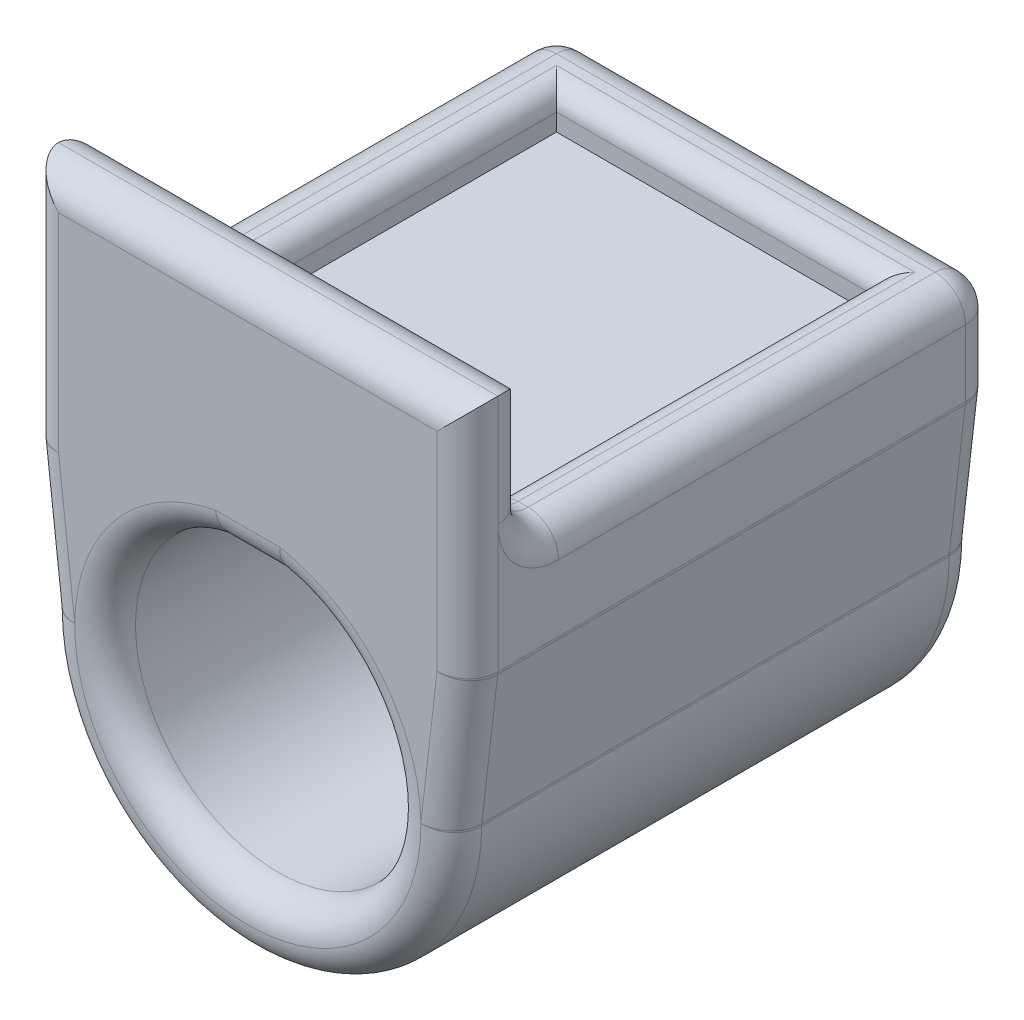
SolidWorks part; units mm, degrees
ref_plane "Front Plane" through (0, 0, 0) normal (0, 0, 1) x (1, 0, 0)
ref_plane "Top Plane" through (0, 0, 0) normal (0, 1, 0) x (1, 0, 0)
ref_plane "Right Plane" through (0, 0, 0) normal (1, 0, 0) x (0, 0, -1)
sketch "Sketch1" plane through (0, 0, 0) normal (0, 1, 0) x (1, 0, 0)
  line L0 (-0.15, -0.15) -> (-0.15, 19.95)
  line L1 (0, 0) -> (15.4, 0) construction
  line L2 (0, 0) -> (0, 19.8) construction
  line L3 (0, 19.8) -> (15.4, 19.8) construction
  line L4 (15.4, 0) -> (15.4, 19.8) construction
  line L5 (-0.15, 19.95) -> (15.55, 19.95)
  line L6 (15.55, -0.15) -> (15.55, 19.95)
  line L7 (-0.15, -0.15) -> (15.55, -0.15)
  line L8 (-3.15, -3.15) -> (18.55, -3.15)
  line L9 (18.55, -3.15) -> (18.55, 22.95)
  line L10 (-3.15, 22.95) -> (18.55, 22.95)
  line L11 (-3.15, -3.15) -> (-3.15, 22.95)
  dimension "D1" = 15.4
  dimension "D2" = 19.8
  dimension "D3" = 0.15
  dimension "D4" = 3
extrude "Boss-Extrude1" add sketch "Sketch1" along normal blind 1.85
extrude "Boss-Extrude2" add sketch "Sketch1<2>" against normal blind 3 contours L0 L7 L6 L5 | L11 L8 L9 L10 L7 L0 L5 L6 region at (7.7, 0, -9.9) region at (-2.8106, 0, -9.9)
sketch "Sketch1<2>" plane through (0, 0, 0) normal (0, 1, 0) x (1, 0, 0) same geometry as "Sketch1"
sketch "Sketch2" plane through (0, 0, 3.15) normal (0, 0, 1) x (1, 0, 0)
  line L0 (7.7, -9.9) -> (7.7, 0) construction
  line L3 (-3.15, -3) -> (18.55, -3) construction
  line L4 (-2.35, -9.9) -> (-3.15, -3)
  line L9 (17.75, -9.9) -> (18.55, -3)
  line L12 (-0.15, 0) -> (15.55, 0) construction
  line L13 (-0.15, 0) -> (15.55, 0)
  circle A6 centre (7.7, -9.9) radius 6.9 construction
  circle A7 centre (7.7, -9.9) radius 7.05
  circle A8 centre (7.7, -9.9) radius 10.05
  line M18 (-3.15, -3) -> (18.55, -3)
  dimension "D6" = 13.8
  dimension "D1" = 0.15
  dimension "D2" = 3
extrude "Boss-Extrude3" add sketch "Sketch2" against normal through all contours A8 L4 M18 | A8 L9 M18 | A8 A7 M18 region at (-1.3948, -6.2845, 3.15) region at (-1.8897, -4.8733, 3.15) region at (17.2897, -4.8733, 3.15)
sketch "Sketch3" plane through (0, 1.85, 0) normal (0, 1, 0) x (1, 0, 0)
  line L0 (-3.15, 22.95) -> (-3.15, -3.15) construction
  line L1 (18.55, -3.15) -> (-3.15, -3.15)
  line L2 (18.55, -3.15) -> (18.55, -0.15)
  line L3 (18.55, -0.15) -> (-3.15, -0.15)
  line L4 (-3.15, -3.15) -> (-3.15, -0.15)
  line L7 (-0.15, -0.15) -> (15.55, -0.15) construction
extrude "Boss-Extrude4" add sketch "Sketch3" along normal blind 7
fillet "Fillet1" radius 1.5 23 edges at (-3.15, -0.575, -22.95) (18.55, -0.575, -22.95) (18.55, 2.925, 3.15) (-3.15, 2.925, 3.15) (-3.15, 1.85, -11.4) (7.7, 1.85, -22.95) (18.55, 1.85, -11.4) (7.7, -3, -22.95) (7.7, 8.85, 3.15) (7.7, -3, 3.15) (17.05, 1.85, 0.15) (18.55, 5.35, 0.15) (7.7, 8.85, 0.15) (-3.15, 5.35, 0.15) (-1.65, 1.85, 0.15) (18.15, -6.45, 3.15) (7.7, -19.95, 3.15) (-2.75, -6.45, 3.15) (7.7, -19.95, -22.95) (18.15, -6.45, -22.95) (-2.75, -6.45, -22.95) (7.7, -16.95, -22.95) (7.7, -16.95, 3.15)
fillet "Fillet2" radius 1 17 edges at (-0.15, 2.2893, -0.2893) (15.55, 2.2893, -0.2893) (-0.15, 1.85, -10.65) (15.55, 1.85, -10.65) (7.7, 1.85, -19.95) (-2.0222, -9.8812, -22.3858) (-2.0222, -9.8812, 2.5858) (-2.7107, -2.9746, 2.7107) (-2.7107, -2.9746, -22.5107) (17.4222, -9.8812, -22.3858) (17.4222, -9.8812, 2.5858) (18.1107, -2.9746, 2.7107) (18.1107, -2.9746, -22.5107) (-2.35, -9.9, -9.9) (-3.15, -3, -9.9) (17.75, -9.9, -9.9) (18.55, -3, -9.9)
